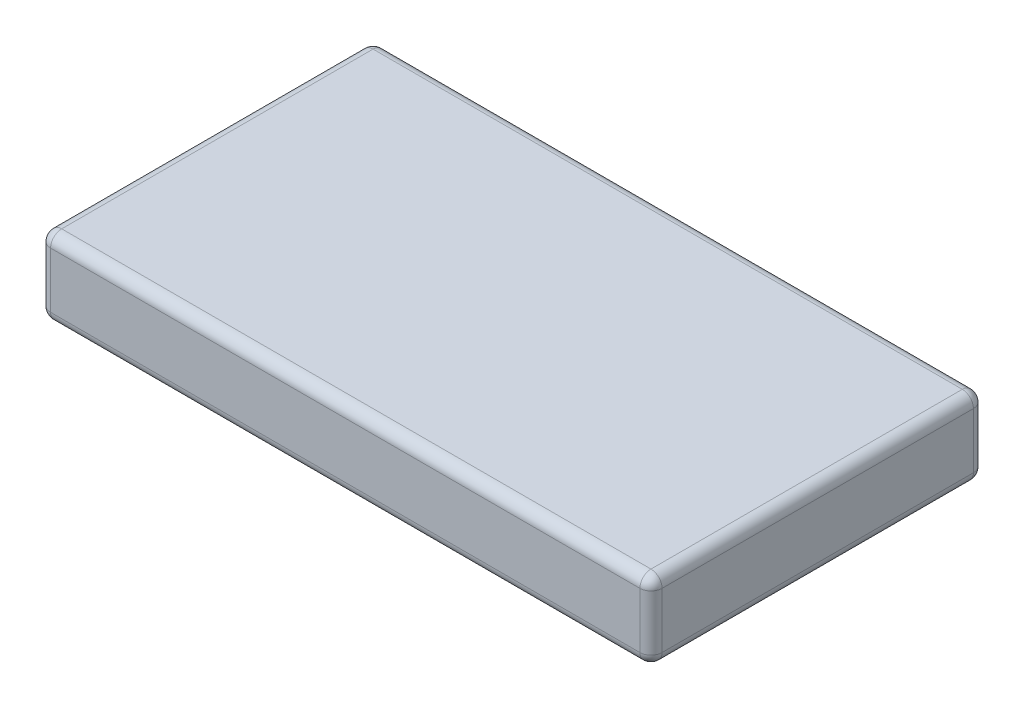
SolidWorks part; units mm, degrees
ref_plane "Front Plane" through (0, 0, 0) normal (0, 0, 1) x (1, 0, 0)
ref_plane "Top Plane" through (0, 0, 0) normal (0, 1, 0) x (1, 0, 0)
ref_plane "Right Plane" through (0, 0, 0) normal (1, 0, 0) x (0, 0, -1)
sketch "Sketch1" plane through (0, 0, 0) normal (0, 1, 0) x (1, 0, 0)
  line L1 (-27.5, 15) -> (27.5, 15)
  line L2 (-27.5, 15) -> (-27.5, -15)
  line L3 (-27.5, -15) -> (27.5, -15)
  line L4 (27.5, 15) -> (27.5, -15)
  line L5 (-27.5, 15) -> (27.5, -15) construction
  line L6 (-27.5, -15) -> (27.5, 15) construction
  point P0 (0, 0)
  dimension "D1" = 30
  dimension "D2" = 55
extrude "Boss-Extrude1" add sketch "Sketch1" along normal blind 7
fillet "Fillet1" radius 1 12 edges at (-27.5, 3.5, -15) (27.5, 3.5, -15) (-27.5, 7, 0) (0, 7, -15) (27.5, 7, 0) (-27.5, 3.5, 15) (0, 7, 15) (27.5, 3.5, 15) (0, 0, -15) (-27.5, 0, 0) (0, 0, 15) (27.5, 0, 0)
